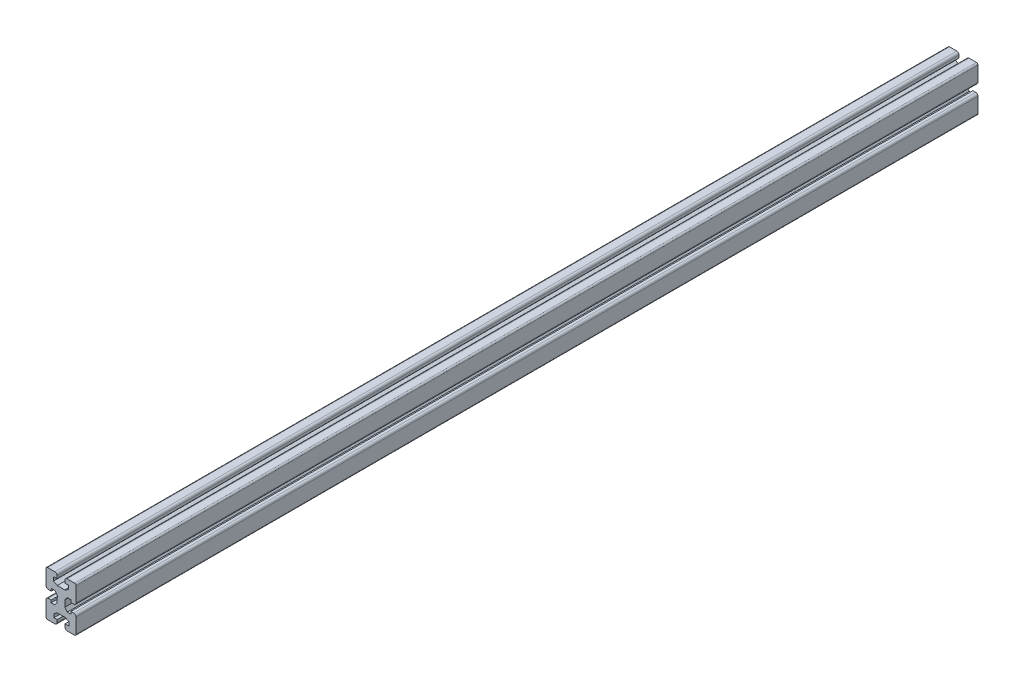
SolidWorks part; units mm, degrees
ref_plane "Alzado" through (0, 0, 0) normal (0, 0, 1) x (1, 0, 0)
ref_plane "Planta" through (0, 0, 0) normal (0, 1, 0) x (1, 0, 0)
ref_plane "Vista lateral" through (0, 0, 0) normal (1, 0, 0) x (0, 0, -1)
sketch "Croquis1" plane through (0, 0, 0) normal (0, 0, 1) x (1, 0, 0)
  line L0 (0, 0) -> (-20, 0) construction
  line L1 (20, -30) -> (5.2, -30)
  line L2 (20, -30) -> (20, -5)
  line L3 (20, 30) -> (5.2, 30)
  line L4 (-20, -30) -> (-20, -5)
  line L5 (20, -30) -> (-20, 30) construction
  line L6 (20, 30) -> (-20, -30) construction
  line L7 (-5.2, -5) -> (5.2, -5)
  line L8 (-5.2, -5) -> (-5.2, 5)
  line L9 (-5.2, 5) -> (5.2, 5)
  line L10 (5.2, -5) -> (5.2, 5)
  line L11 (-5.2, -5) -> (5.2, 5) construction
  line L12 (-5.2, 5) -> (5.2, -5) construction
  line L14 (10, -5) -> (10, 5.215)
  line L16 (-10, -5) -> (-10, 5.215)
  line L17 (10, -10) -> (-10, 10) construction
  line L18 (10, 10) -> (-10, -10) construction
  line L19 (0, 0) -> (0, 10) construction
  line L20 (-10, 5.215) -> (-20, 5.215)
  line L21 (-10, -5) -> (-20, -5)
  line L22 (10, -5) -> (20, -5)
  line L23 (20, 5.215) -> (10, 5.215)
  line L24 (-5.2, 20) -> (-5.2, 30)
  line L25 (5.2, 20) -> (5.2, 30)
  line L26 (5.2, -20) -> (5.2, -30)
  line L27 (-5.2, -20) -> (-5.2, -30)
  line L28 (20, 5.215) -> (20, 30)
  line L29 (-5.2, -30) -> (-20, -30)
  line L30 (-5.2, 30) -> (-20, 30)
  line L32 (-20, 5.215) -> (-20, 30)
  line L33 (-5.2, -30) -> (5.2, -30) construction
  line L34 (0, -30) -> (0, -20) construction
  line L36 (-5.2, -20) -> (5.2, -20)
  line L37 (-5.2, 20) -> (5.2, 20)
  point P0 (0, 0)
  point P6 (0, 0)
  point P11 (0, 0)
  dimension "D1" = 40
  dimension "D2" = 60
  dimension "D3" = 10
  dimension "D4" = 5.2
  dimension "D5" = 20
  dimension "D6" = 20
  dimension "D7" = 10
extrude "Saliente-Extruir1" add sketch "Croquis1" along normal blind 1200 contours L26 L1 L2 L22 L14 L23 L28 L3 L25 L37 L24 L30 L32 L20 L16 L21 L4 L29 L27 L36
fillet "Redondeo3" radius 2 4 edges at (-20, -30, 600) (20, -30, 600) (20, 30, 600) (-20, 30, 600)
fillet "Redondeo4" radius 3 8 edges at (5.2, 30, 600) (20, -5, 600) (20, 5.215, 600) (-5.2, 30, 600) (-20, -5, 600) (-20, 5.215, 600) (5.2, -30, 600) (-5.2, -30, 600)
sketch "Croquis2" plane through (0, 0, 1200) normal (0, 0, 1) x (1, 0, 0)
  line L0 (0, 0) -> (0, 20) construction
  line L1 (-5.2, 20) -> (5.2, 20) construction
  line L2 (0, 20) -> (0, 23.452) construction
  line L3 (-10, 23.452) -> (10, 23.452)
  line L4 (10, 23.452) -> (10, 18.452)
  line L5 (10, 18.452) -> (5, 15.7561)
  line L6 (5, 15.7561) -> (-5, 15.7561)
  line L7 (-10, 18.452) -> (-5, 15.7561)
  line L8 (-10, 23.452) -> (-10, 18.452)
  line L9 (0, 0) -> (10, 0.1075) construction
  line L10 (10, -5) -> (10, 5.215) construction
  line L11 (-9.601, -18.6627) -> (-4.6601, -15.8599)
  line L12 (-9.4935, -23.6616) -> (-9.601, -18.6627)
  line L13 (-9.4935, -23.6616) -> (10.5018, -23.2316)
  line L14 (10.5018, -23.2316) -> (10.3944, -18.2328)
  line L15 (10.3944, -18.2328) -> (5.3376, -15.6449)
  line L16 (5.3376, -15.6449) -> (-4.6601, -15.8599)
  line L17 (10, 0.1075) -> (13, 0.1075) construction
  line L18 (13, 0.1075) -> (13, 0.1397)
  line L19 (13, 8.4777) -> (8.1055, 8.4777)
  line L20 (8.1055, 8.4777) -> (5, 4.2926)
  line L22 (8.2859, -8.3015) -> (5.0911, -4.1841)
  line L23 (12.9993, 0.172) -> (13, 0.1397)
  line L24 (13.1792, -8.1962) -> (8.2859, -8.3015)
  line L26 (13, 8.4777) -> (13.1792, -8.1962)
  line L27 (5, 4.2926) -> (5.0911, -4.1841)
  line L28 (-13, 8.4777) -> (-8.1055, 8.4777)
  line L29 (-13, 8.4777) -> (-13.1792, -8.1962)
  line L30 (-13.1792, -8.1962) -> (-8.2859, -8.3015)
  line L31 (-8.2859, -8.3015) -> (-5.0911, -4.1841)
  line L32 (-5, 4.2926) -> (-5.0911, -4.1841)
  line L33 (-8.1055, 8.4777) -> (-5, 4.2926)
  point P11 (0, 15.7561)
  line M22 (5.2, 27) -> (5.2, 20)
  line M23 (5.2, 20) -> (-5.2, 20)
  line M24 (-5.2, 20) -> (-5.2, 27)
  line M30 (-17, 5.215) -> (-10, 5.215)
  line M31 (-10, 5.215) -> (-10, -5)
  line M32 (-10, -5) -> (-17, -5)
  line M38 (-5.2, -27) -> (-5.2, -20)
  line M39 (-5.2, -20) -> (5.2, -20)
  line M40 (5.2, -20) -> (5.2, -27)
  line M46 (17, -5) -> (10, -5)
  line M47 (10, -5) -> (10, 5.215)
  line M48 (10, 5.215) -> (17, 5.215)
  dimension "D1" = 5
  dimension "D2" = 10
  dimension "D3" = 20
  dimension "D4" = 8.4767
extrude "Cortar-Extruir1" cut sketch "Croquis2" against normal blind 1200 contours L3 L8 L7 L6 L5 L4 M22 M23 M24 | L33 L28 L29 L30 L31 L32 M30 M31 M32 | L15 L16 L11 L12 L13 L14 M38 M39 M40 | L20 L27 L22 L24 L26 L19 M46 M47 M48 | L26 | L29 M30 M32 M31 | L3 M24 M23 M22 | L13 M38 M40 M39 region at (0, 19.2556, 1200) region at (0, 21.726, 1200) region at (0.5939, -19.247, 1200) region at (-0.0561, -21.7293, 1200) region at (8.6241, 0.1091, 1200) region at (11.5452, 0.0772, 1200) region at (-8.6241, 0.1091, 1200) region at (-11.5452, 0.0772, 1200)
